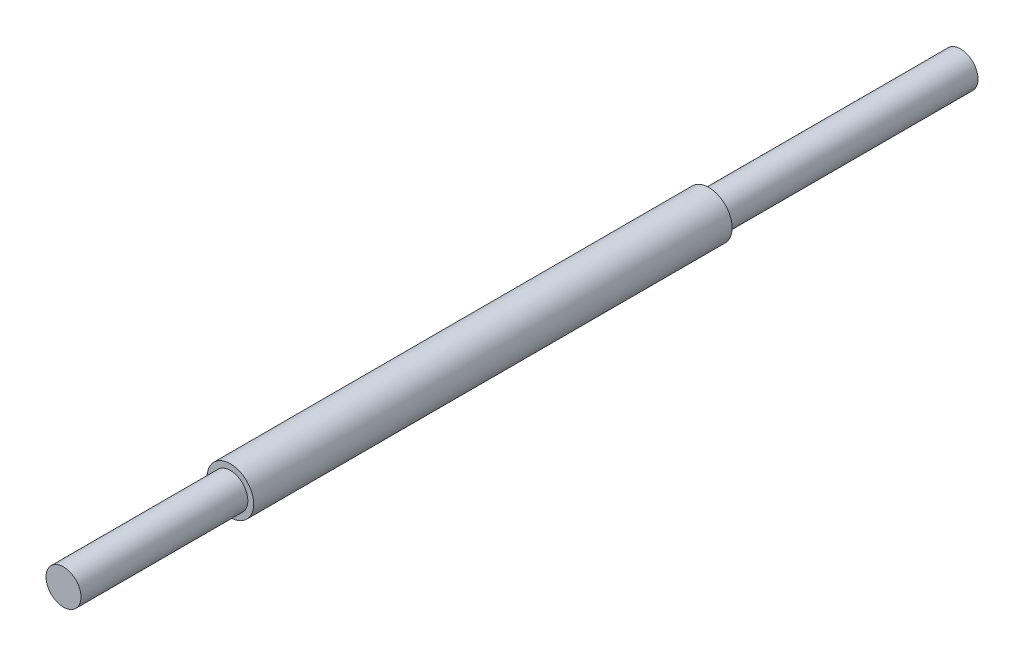
SolidWorks part; units mm, degrees
material "AISI 1020"
ref_plane "Front Plane" through (0, 0, 0) normal (0, 0, 1) x (1, 0, 0)
ref_plane "Top Plane" through (0, 0, 0) normal (0, 1, 0) x (1, 0, 0)
ref_plane "Right Plane" through (0, 0, 0) normal (1, 0, 0) x (0, 0, -1)
sketch "Sketch1" plane through (0, 0, 0) normal (0, 0, 1) x (1, 0, 0)
  circle A0 centre (0, 0) radius 6.35
  dimension "D1" = 12.7
extrude "Boss-Extrude1" add sketch "Sketch1" along normal blind 130.3528
sketch "Sketch2" plane through (0, 0, 130.3528) normal (0, 0, 1) x (1, 0, 0)
  circle A0 centre (0, 0) radius 4.7625
  dimension "D1" = 9.525
extrude "Boss-Extrude2" add sketch "Sketch2" along normal blind 45.466
sketch "Sketch3" plane through (0, 0, 0) normal (0, 0, -1) x (-1, 0, 0)
  circle A0 centre (0, 0) radius 4.7625
  dimension "D1" = 9.525
extrude "Boss-Extrude3" add sketch "Sketch3" along normal blind 68.58
sketch "Sketch4" plane through (0, 0, 0) normal (0, 1, 0) x (1, 0, 0)
  line L0 (4.7625, -175.8188) -> (4.7625, -176.0537)
  line L1 (52.578, -176.0537) -> (-52.578, -176.0537) construction
  line L2 (4.7625, -175.8188) -> (4.7625, -130.3528) construction
  line L3 (4.7625, -176.0537) -> (4.445, -176.0537)
  line L4 (4.445, -176.0537) -> (4.445, -175.8188)
  line L5 (-4.7625, -175.8188) -> (4.7625, -175.8188) construction
  line L6 (4.445, -175.8188) -> (4.7625, -175.8188)
  line L7 (0, -175.8188) -> (0, -171.0494) construction
  line L8 (0, -146.88) -> (0, -215.9928) construction
  dimension "D1" = 8.89
